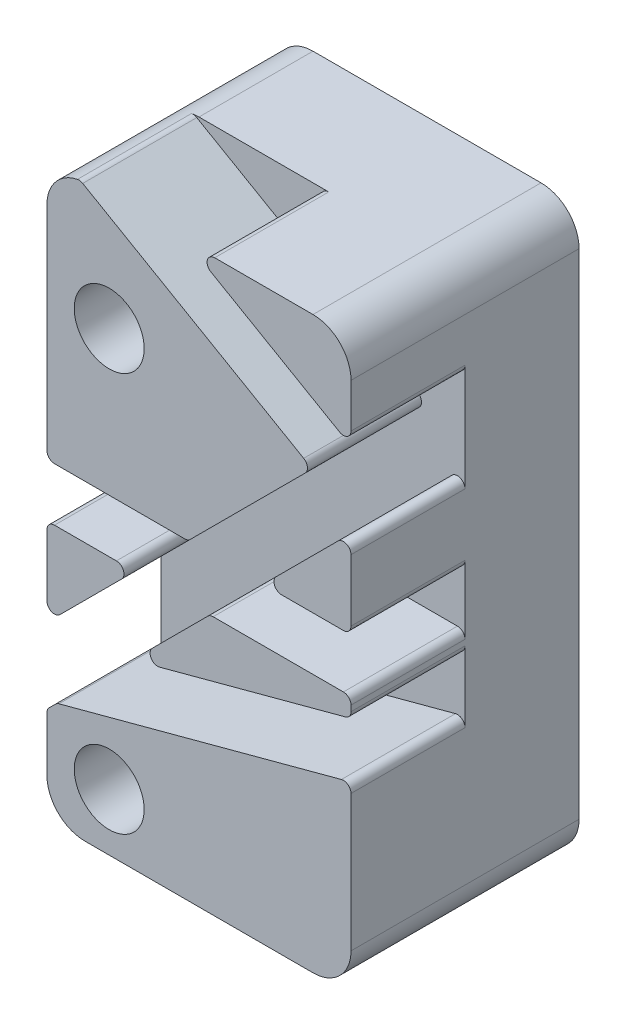
SolidWorks part; units mm, degrees
ref_plane "Front" through (0, 0, 0) normal (0, 0, 1) x (1, 0, 0)
ref_plane "Top" through (0, 0, 0) normal (0, 1, 0) x (1, 0, 0)
ref_plane "Right" through (0, 0, 0) normal (1, 0, 0) x (0, 0, -1)
sketch "Sketch1" plane through (0, 0, 0) normal (0, 0, 1) x (1, 0, 0)
  line L1 (-25.4, -47.625) -> (25.4, -47.625)
  line L2 (-25.4, -47.625) -> (-25.4, 47.625)
  line L3 (-25.4, 47.625) -> (25.4, 47.625)
  line L4 (25.4, -47.625) -> (25.4, 47.625)
  line L5 (-25.4, -47.625) -> (25.4, 47.625) construction
  line L6 (-25.4, 47.625) -> (25.4, -47.625) construction
  point P0 (0, 0)
  dimension "D1" = 50.8
  dimension "D2" = 95.25
extrude "Boss-Extrude1" add sketch "Sketch1" along normal blind 38.1
sketch "Sketch2" plane through (0, 0, 38.1) normal (0, 0, 1) x (1, 0, 0)
  line L1 (-37.1277, -4.445) -> (37.1277, -4.445)
  line L2 (-37.1277, -4.445) -> (-37.1277, 4.445)
  line L3 (-37.1277, 4.445) -> (37.1277, 4.445)
  line L4 (37.1277, -4.445) -> (37.1277, 4.445)
  line L5 (-37.1277, -4.445) -> (37.1277, 4.445) construction
  line L6 (-37.1277, 4.445) -> (37.1277, -4.445) construction
  point P0 (0, 0)
  dimension "D1" = 8.89
extrude "0 deg slot" cut sketch "Sketch2" against normal blind 19.05
sketch "Sketch3" plane through (0, 0, 0) normal (0, 0, -1) x (-1, 0, 0)
  line L0 (0, -47.625) -> (0, 47.625) construction
  line L1 (25.4, -47.625) -> (-25.4, -47.625) construction
  line L2 (-25.4, 47.625) -> (25.4, 47.625) construction
  line L3 (0, 0) -> (-15, 0) construction
  line L4 (-17.5146, -38.1) -> (-12.4854, -38.1)
  line L5 (-17.5146, -38.1) -> (-17.5146, 38.1)
  line L6 (-17.5146, 38.1) -> (-12.4854, 38.1)
  line L7 (-12.4854, -38.1) -> (-12.4854, 38.1)
  line L8 (-17.5146, -38.1) -> (-12.4854, 38.1) construction
  line L9 (-17.5146, 38.1) -> (-12.4854, -38.1) construction
  point P6 (-15, 0)
  dimension "D1" = 5.0292
  dimension "D2" = 15
  dimension "D3" = 76.2
extrude "Boss-Extrude2" add sketch "Sketch3" along normal blind 6.35
sketch "Sketch4" plane through (0, 0, 0) normal (0, 0, -1) x (-1, 0, 0)
  line L0 (15, 47.625) -> (15, -47.625) construction
  line L1 (-25.4, 47.625) -> (25.4, 47.625) construction
  line L2 (25.4, -47.625) -> (-25.4, -47.625) construction
  circle A0 centre (15, 28.575) radius 4.9022
  circle A1 centre (15, -38.1) radius 4.9022
  dimension "D2" = 9.8044
  dimension "D3" = 9.8044
  dimension "D1" = 15
  dimension "D4" = 28.575
  dimension "D5" = 38.1
extrude "Cut-Extrude2" cut sketch "Sketch4" against normal through all
sketch "Sketch5" plane through (0, 0, 38.1) normal (0, 0, 1) x (1, 0, 0)
  circle A0 centre (-15, -38.1) radius 5.842
  circle A1 centre (-15, 28.575) radius 5.842
  dimension "D1" = 11.684
  dimension "D2" = 11.684
extrude "Cut-Extrude3" cut sketch "Sketch5" against normal offset from surface (12.319 mm away) 25.781 up to face at (-19.9022, -38.1, 0)
sketch "Sketch6" plane through (0, 0, 38.1) normal (0, 0, 1) x (1, 0, 0)
  line L0 (42.9773, 49.2634) -> (-49.2634, -42.9773)
  line L1 (-49.2634, -42.9773) -> (-42.9773, -49.2634)
  line L2 (-42.9773, -49.2634) -> (49.2634, 42.9773)
  line L3 (49.2634, 42.9773) -> (42.9773, 49.2634)
  line L4 (-46.1204, -46.1204) -> (46.1204, 46.1204) construction
  line L5 (-25.4, 4.445) -> (25.4, 4.445) construction
  point P7 (0, 0)
  dimension "D1" = 8.89
  dimension "D2" = 45
extrude "45deg slot" cut sketch "Sketch6" against normal up to surface (19.05 mm away) up to face at (0, 0, 19.05)
sketch "Sketch7" plane through (0, 0, 38.1) normal (0, 0, 1) x (1, 0, 0)
  line L0 (48.9697, 7.8697) -> (-53.4147, 66.9813)
  line L1 (-53.4147, 66.9813) -> (-48.9697, 74.6803)
  line L2 (-48.9697, 74.6803) -> (53.4147, 15.5687)
  line L3 (53.4147, 15.5687) -> (48.9697, 7.8697)
  line L4 (-51.1922, 70.8308) -> (51.1922, 11.7192) construction
  line L6 (25.4, -4.445) -> (1.8412, -4.445) construction
  line L7 (0, 41.275) -> (0, 0) construction
  point P6 (0, 41.275)
  point P16 (0, 0)
  dimension "D3" = 41.275
  dimension "D1" = 8.89
  dimension "D2" = 30
extrude "30 deg slot" cut sketch "Sketch7" against normal up to surface (19.05 mm away) up to face at (0, 0, 19.05)
fillet "Fillet2" radius 6.35 4 edges at (-25.4, -47.625, 19.05) (25.4, -47.625, 19.05) (25.4, 47.625, 19.05) (-25.4, 47.625, 19.05)
sketch "Sketch8" plane through (0, 0, 38.1) normal (0, 0, 1) x (1, 0, 0)
  line L1 (25.6286, -50.165) -> (-25.6286, -50.165) construction
  line L2 (25.6286, -50.165) -> (25.6286, 50.165) construction
  line L3 (25.6286, 50.165) -> (-25.6286, 50.165) construction
  line L4 (-25.6286, -50.165) -> (-25.6286, 50.165) construction
  line L5 (25.6286, -50.165) -> (-25.6286, 50.165) construction
  line L6 (25.6286, 50.165) -> (-25.6286, -50.165) construction
  point P0 (0, 0)
  dimension "D1" = 51.2572
  dimension "D2" = 100.33
sketch "Sketch9" plane through (0, 0, 0) normal (0, 0, -1) x (-1, 0, 0)
  line L4 (-25.4, -41.275) -> (-25.4, 41.275)
  line L5 (-19.05, 47.625) -> (19.05, 47.625)
  line L6 (25.4, 41.275) -> (25.4, -41.275)
  line L7 (19.05, -47.625) -> (-19.05, -47.625)
  arc A2 (19.05, -47.625) -> (25.4, -41.275) centre (19.05, -41.275) ccw construction
  arc A3 (-19.05, -47.625) -> (-25.4, -41.275) centre (-19.05, -41.275) cw
  arc A4 (-25.4, 41.275) -> (-19.05, 47.625) centre (-19.05, 41.275) cw
  arc A5 (19.05, 47.625) -> (25.4, 41.275) centre (19.05, 41.275) cw
  arc A6 (25.4, -41.275) -> (19.05, -47.625) centre (19.05, -41.275) cw
sketch "Sketch10" plane through (0, 0, 38.1) normal (0, 0, 1) x (1, 0, 0)
  line L0 (55.7071, -8.7251) -> (-53.4062, -37.962)
  line L1 (-53.4062, -37.962) -> (-55.7071, -29.3749)
  line L2 (-55.7071, -29.3749) -> (53.4062, -0.138)
  line L3 (53.4062, -0.138) -> (55.7071, -8.7251)
  line L4 (-54.5567, -33.6684) -> (54.5567, -4.4316) construction
  line L5 (25.6286, -50.165) -> (-25.6286, -50.165) construction
  line L6 (0, 0) -> (0, -19.05) construction
  point P6 (0, -19.05)
  dimension "D1" = 15
  dimension "D2" = 8.89
  dimension "D3" = 19.05
extrude "15 deg slot" cut sketch "Sketch10" against normal up to surface (19.05 mm away) up to face at (-1.3775, 10.507, 19.05)
fillet "Fillet4" radius 2.5146 4 edges at (12.4854, 38.1, -3.175) (17.5146, 38.1, -3.175) (17.5146, -38.1, -3.175) (12.4854, -38.1, -3.175)
fillet "Fillet3" radius 1.27 19 edges at (25.4, 19.1138, 28.575) (25.4, 4.445, 28.575) (25.4, -4.445, 28.575) (-25.4, -31.6862, 28.575) (-25.4, 4.445, 28.575) (-25.4, -4.445, 28.575) (-25.4, -19.1138, 28.575) (-1.8412, 4.445, 28.575) (-10.7312, -4.445, 28.575) (1.8412, -4.445, 28.575) (10.7312, 4.445, 28.575) (-2.1085, 47.625, 28.575) (25.4, 31.7429, 28.575) (18.9281, 25.2142, 28.575) (-19.8096, 47.5794, 28.575) (25.4, -7.6423, 28.575) (25.4, -16.8459, 28.575) (-11.1495, -17.4357, 28.575) (-23.7219, -30.0081, 28.575)
sketch "Sketch12" plane through (0, 0, -6.35) normal (0, 0, -1) x (-1, 0, 0)
  line L0 (19.05, -47.625) -> (-19.05, -47.625) construction
  line L1 (-25.4, 47.625) -> (25.4, 47.625)
  line L2 (-25.4, 47.625) -> (-25.4, -47.625)
  line L3 (-25.4, -47.625) -> (25.4, -47.625)
  line L4 (25.4, 47.625) -> (25.4, -47.625)
  line L5 (-25.4, 47.625) -> (25.4, -47.625) construction
  line L6 (-25.4, -47.625) -> (25.4, 47.625) construction
  line L7 (25.4, 41.275) -> (25.4, -41.275) construction
  point P0 (0, 0)
ref_plane "Plane1" through (0, 0, -9.0932) normal (0, 0, -1) x (-1, 0, 0)
sketch "Sketch13" plane through (0, 0, -9.0932) normal (0, 0, -1) x (-1, 0, 0)
  line L0 (-25.4, -41.275) -> (-25.4, 41.275) construction
  line L1 (25.4, -47.625) -> (-25.4, -47.625)
  line L2 (25.4, -47.625) -> (25.4, 47.625)
  line L3 (25.4, 47.625) -> (-25.4, 47.625)
  line L4 (-25.4, -47.625) -> (-25.4, 47.625)
  line L5 (25.4, -47.625) -> (-25.4, 47.625) construction
  line L6 (25.4, 47.625) -> (-25.4, -47.625) construction
  line L7 (-19.05, 47.625) -> (19.05, 47.625) construction
  point P0 (0, 0)
